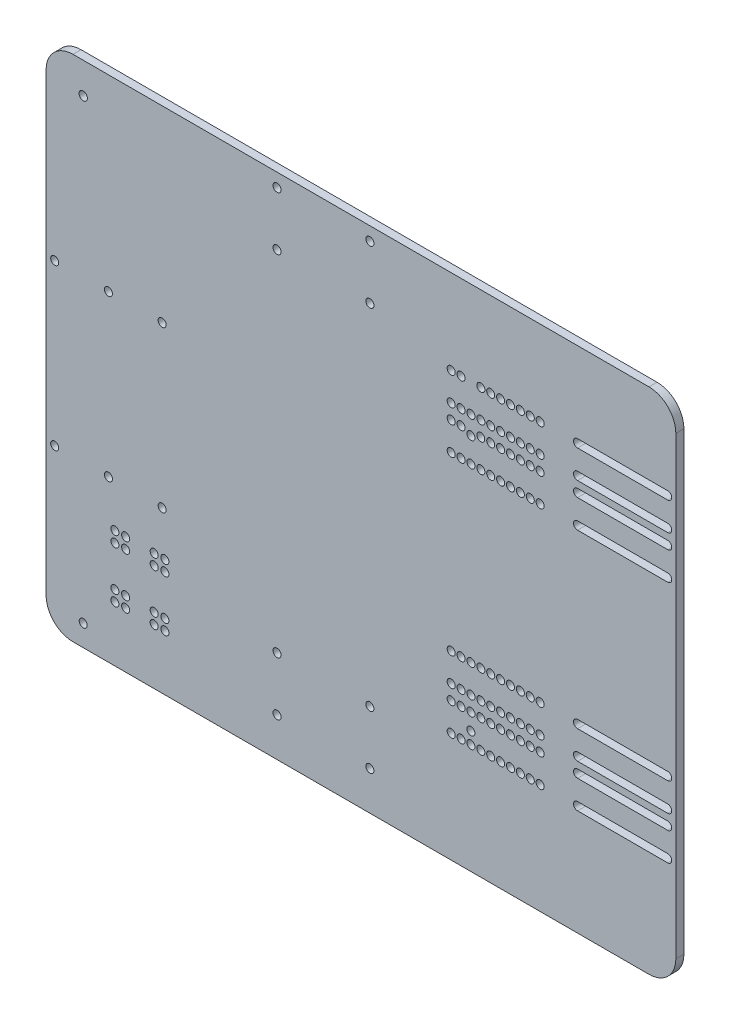
SolidWorks part; units mm, degrees
ref_plane "前视基准面" through (0, 0, 0) normal (0, 0, 1) x (1, 0, 0)
ref_plane "上视基准面" through (0, 0, 0) normal (0, 1, 0) x (1, 0, 0)
ref_plane "右视基准面" through (0, 0, 0) normal (1, 0, 0) x (0, 0, -1)
sketch "草图1" plane through (0, 0, 0) normal (0, 0, 1) x (1, 0, 0)
  line L1 (-115.5855, 94.5486) -> (118.873, 94.5486)
  line L2 (-115.5855, 94.5486) -> (-115.5855, -94.8828)
  line L3 (-115.5855, -94.8828) -> (118.873, -94.8828)
  line L4 (118.873, 94.5486) -> (118.873, -94.8828)
  circle A3 centre (-72.3857, 24.6381) radius 1.5
  circle A16 centre (-72.3857, -35.082) radius 1.5
extrude "凸台-拉伸1" add sketch "草图1" along normal blind 3
fillet "圆角1" radius 10 4 edges at (118.873, 94.5486, 1.5) (-115.5855, 94.5486, 1.5) (-115.5855, -94.8828, 1.5) (118.873, -94.8828, 1.5)
sketch "草图2" plane through (0, 0, 3) normal (0, 0, 1) x (1, 0, 0)
  line L1 (-105.5855, -94.8828) -> (108.873, -94.8828) construction
  circle A0 centre (-71.363, -51.2228) radius 1.5
  circle A1 centre (-71.363, -70.2228) radius 1.5
  circle A2 centre (-85.983, -51.2228) radius 1.5
  circle A3 centre (-85.983, -70.2228) radius 1.5
  circle A8 centre (-85.983, -51.2228) radius 1.5
  circle A9 centre (-71.363, -51.2228) radius 1.5
  circle A10 centre (-85.983, -70.2228) radius 1.5
  circle A11 centre (-71.363, -70.2228) radius 1.5
  circle A12 centre (-89.983, -51.2228) radius 1.5
  circle A13 centre (-75.363, -51.2228) radius 1.5
  circle A14 centre (-89.983, -70.2228) radius 1.5
  circle A15 centre (-75.363, -70.2228) radius 1.5
  circle A28 centre (-85.983, -51.2228) radius 1.5
  circle A29 centre (-71.363, -51.2228) radius 1.5
  circle A30 centre (-85.983, -70.2228) radius 1.5
  circle A31 centre (-71.363, -70.2228) radius 1.5
  circle A32 centre (-89.983, -51.2228) radius 1.5
  circle A34 centre (-75.363, -51.2228) radius 1.5
  circle A36 centre (-89.983, -70.2228) radius 1.5
  circle A38 centre (-75.363, -70.2228) radius 1.5
  circle A40 centre (-85.983, -55.2228) radius 1.5
  circle A41 centre (-71.363, -55.2228) radius 1.5
  circle A42 centre (-85.983, -74.2228) radius 1.5
  circle A43 centre (-71.363, -74.2228) radius 1.5
  circle A44 centre (-89.983, -55.2228) radius 1.5
  circle A46 centre (-75.363, -55.2228) radius 1.5
  circle A48 centre (-89.983, -74.2228) radius 1.5
  circle A50 centre (-75.363, -74.2228) radius 1.5
  circle A52 centre (-89.983, -47.2228) radius 1.5 [skipped]
  circle A53 centre (-85.983, -47.2228) radius 1.5 [skipped]
  circle A55 centre (-75.363, -47.2228) radius 1.5 [skipped]
  circle A56 centre (-71.363, -47.2228) radius 1.5 [skipped]
  circle A58 centre (-89.983, -66.2228) radius 1.5 [skipped]
  circle A59 centre (-85.983, -66.2228) radius 1.5 [skipped]
  circle A61 centre (-75.363, -66.2228) radius 1.5 [skipped]
  circle A62 centre (-71.363, -66.2228) radius 1.5 [skipped]
  circle A64 centre (-81.983, -51.2228) radius 1.5 [skipped]
  circle A65 centre (-81.983, -70.2228) radius 1.5 [skipped]
  circle A66 centre (-67.363, -51.2228) radius 1.5 [skipped]
  circle A67 centre (-67.363, -70.2228) radius 1.5 [skipped]
  dimension "D1" = 3
  dimension "D5" = 3
  dimension "D6" = 3
  dimension "D7" = 14.62
  dimension "D8" = 3
  dimension "D3" = 43.66
  dimension "D4" = 19
  dimension "D9" = 2
  dimension "D10" = 2
  dimension "D11" = 2
  dimension "D12" = 2
extrude "切除-拉伸1" cut sketch "草图2" against normal through all contours A48 | A0 | A13 | A2 | A12 | A44 | A40 | A46 | A41 | A1 | A15 | A3 | A14 | A42 | A50 | A43 region at (-89.983, -74.2228, 3)
sketch "草图4" plane through (0, 0, 3) normal (0, 0, 1) x (1, 0, 0)
  circle A4 centre (-101.767, 83.0486) radius 1.5704
  circle A5 centre (-101.767, -86.9514) radius 1.5
  circle A6 centre (42.5819, 45.6694) radius 1.5
  circle A7 centre (42.5819, -49.5721) radius 1.5
  circle A13 centre (-112.3857, 24.6381) radius 1.5
  circle A16 centre (-112.3857, -35.082) radius 1.5
  circle A17 centre (-92.3857, 24.6381) radius 1.5
  circle A18 centre (-92.3857, -35.082) radius 1.5
extrude "切除-拉伸2" cut sketch "草图4" against normal through all
sketch "草图6" plane through (0, 0, 3) normal (0, 0, 1) x (1, 0, 0)
  line L0 (-37.3236, 94.5486) -> (-16.1289, 94.5486)
  line L1 (-37.3236, -85.4514) -> (-37.3236, 94.5486)
  line L2 (-37.3236, -85.4514) -> (12.6764, -85.4514)
  line L3 (12.6764, -85.4514) -> (12.6764, 94.5486)
  line L4 (12.6764, 4.5486) -> (122.1564, 4.5486)
  line L5 (-16.1289, 94.5486) -> (-12.3236, 94.5486)
  line L10 (108.873, 94.5486) -> (-105.5855, 94.5486) construction
  line L11 (-12.3236, 94.5486) -> (12.6764, 94.5486)
  line L12 (47.6764, 111.2587) -> (47.6764, -114.1672)
  line L17 (91.3583, 51.0486) -> (115.854, 51.0486)
  line L19 (155.8937, -35.4514) -> (19.7198, -35.4514)
  line L24 (91.3583, 38.0486) -> (115.854, 38.0486)
  line L25 (91.3583, 35.0486) -> (115.854, 35.0486)
  line L30 (91.3583, 54.0486) -> (115.854, 54.0486)
  line L43 (91.3583, 45.5486) -> (115.854, 45.5486)
  line L44 (91.3583, 61.5486) -> (115.854, 61.5486)
  line L50 (155.8937, 55.0486) -> (23.4823, 55.0486)
  line L53 (91.3583, 64.5486) -> (115.854, 64.5486)
  line L54 (91.3583, 48.5486) -> (115.854, 48.5486)
  line L59 (32.6764, 113.2645) -> (32.6764, -109.5534)
  line L60 (91.3583, 64.5486) -> (82.2736, 64.5486)
  line L62 (82.2736, 61.5486) -> (91.3583, 61.5486)
  line L63 (91.3583, 54.0486) -> (82.2736, 54.0486)
  line L65 (82.2736, 51.0486) -> (91.3583, 51.0486)
  line L66 (91.3583, 48.5486) -> (82.2736, 48.5486)
  line L68 (82.2736, 45.5486) -> (91.3583, 45.5486)
  line L69 (91.3583, 38.0486) -> (82.2736, 38.0486)
  line L71 (82.2736, 35.0486) -> (91.3583, 35.0486)
  line L72 (82.2736, -25.9514) -> (91.3583, -25.9514)
  line L73 (91.3583, -28.9514) -> (82.2736, -28.9514)
  line L74 (82.2736, -36.4514) -> (91.3583, -36.4514)
  line L75 (91.3583, -39.4514) -> (82.2736, -39.4514)
  line L76 (82.2736, -41.9514) -> (91.3583, -41.9514)
  line L77 (91.3583, -44.9514) -> (82.2736, -44.9514)
  line L78 (82.2736, -52.4514) -> (91.3583, -52.4514)
  line L79 (91.3583, -55.4514) -> (82.2736, -55.4514)
  line L80 (91.3583, -39.4514) -> (115.854, -39.4514)
  line L81 (91.3583, -55.4514) -> (115.854, -55.4514)
  line L82 (91.3583, -52.4514) -> (115.854, -52.4514)
  line L83 (91.3583, -36.4514) -> (115.854, -36.4514)
  line L84 (91.3583, -44.9514) -> (115.854, -44.9514)
  line L85 (91.3583, -25.9514) -> (115.854, -25.9514)
  line L86 (91.3583, -28.9514) -> (115.854, -28.9514)
  line L87 (91.3583, -41.9514) -> (115.854, -41.9514)
  circle A14 centre (-29.6096, 89.5486) radius 1.5
  circle A15 centre (4.9625, -60.4514) radius 1.5
  circle A16 centre (-29.6096, -80.4514) radius 1.5
  circle A17 centre (4.9625, -80.4514) radius 1.5
  circle A18 centre (4.9625, 89.5486) radius 1.5
  circle A19 centre (-29.6096, 69.5486) radius 1.5
  circle A20 centre (-29.6096, -60.4514) radius 1.5
  circle A21 centre (-29.6096, -80.4514) radius 1.5
  circle A23 centre (49.9549, -27.4514) radius 1.5
  circle A24 centre (49.9549, -43.4514) radius 1.5
  circle A39 centre (53.6349, -27.4514) radius 1.5
  circle A40 centre (53.6349, -43.4514) radius 1.5
  circle A41 centre (57.3149, -27.4514) radius 1.5
  circle A42 centre (57.3149, -43.4514) radius 1.5
  circle A43 centre (60.9949, -27.4514) radius 1.5
  circle A44 centre (60.9949, -43.4514) radius 1.5
  circle A45 centre (64.6749, -27.4514) radius 1.5
  circle A46 centre (64.6749, -43.4514) radius 1.5
  circle A47 centre (68.3549, -27.4514) radius 1.5
  circle A48 centre (68.3549, -43.4514) radius 1.5
  circle A49 centre (68.3549, 52.5486) radius 1.5
  circle A50 centre (68.3549, 36.5486) radius 1.5
  circle A51 centre (64.6749, 52.5486) radius 1.5
  circle A52 centre (64.6749, 36.5486) radius 1.5
  circle A53 centre (60.9949, 52.5486) radius 1.5
  circle A54 centre (60.9949, 36.5486) radius 1.5
  circle A55 centre (57.3149, 52.5486) radius 1.5
  circle A56 centre (57.3149, 36.5486) radius 1.5
  circle A57 centre (53.6349, 52.5486) radius 1.5
  circle A58 centre (53.6349, 36.5486) radius 1.5
  arc A61 (115.854, 54.0486) -> (115.854, 51.0486) centre (115.854, 52.5486) cw
  arc A62 (115.854, 38.0486) -> (115.854, 35.0486) centre (115.854, 36.5486) cw
  circle A63 centre (49.9549, 52.5486) radius 1.5
  circle A64 centre (49.9549, 36.5486) radius 1.5
  circle A79 centre (68.3549, 63.0486) radius 1.5
  circle A80 centre (49.9549, 63.0486) radius 1.5
  circle A83 centre (57.3149, 63.0486) radius 1.5
  circle A86 centre (64.6749, 47.0486) radius 1.5
  circle A87 centre (49.9549, 47.0486) radius 1.5
  arc A89 (115.854, 48.5486) -> (115.854, 45.5486) centre (115.854, 47.0486) cw
  circle A90 centre (53.6349, 63.0486) radius 1.5
  circle A93 centre (60.9949, 63.0486) radius 1.5
  circle A95 centre (64.6749, 63.0486) radius 1.5
  circle A96 centre (57.3149, 47.0486) radius 1.5
  circle A97 centre (53.6349, 47.0486) radius 1.5
  arc A98 (115.854, 64.5486) -> (115.854, 61.5486) centre (115.854, 63.0486) cw
  circle A99 centre (60.9949, 47.0486) radius 1.5
  circle A100 centre (68.3549, 47.0486) radius 1.5
  circle A101 centre (49.9549, -37.9514) radius 1.5
  circle A102 centre (68.3549, -37.9514) radius 1.5
  circle A103 centre (60.9949, -37.9514) radius 1.5
  circle A104 centre (53.6349, -37.9514) radius 1.5
  circle A105 centre (57.3149, -37.9514) radius 1.5
  circle A109 centre (64.6749, -37.9514) radius 1.5
  circle A112 centre (49.9549, -53.9514) radius 1.5
  circle A114 centre (64.6749, -53.9514) radius 1.5
  circle A115 centre (60.9949, -53.9514) radius 1.5
  circle A117 centre (53.6349, -53.9514) radius 1.5
  circle A121 centre (57.3149, -53.9514) radius 1.5
  circle A122 centre (68.3549, -53.9514) radius 1.5
  circle A123 centre (4.9625, 69.5486) radius 1.5
  circle A124 centre (46.2749, 63.0486) radius 1.5
  circle A125 centre (46.2749, 52.5486) radius 1.5
  circle A126 centre (46.2749, 47.0486) radius 1.5
  circle A127 centre (46.2749, 36.5486) radius 1.5
  circle A128 centre (46.2749, -27.4514) radius 1.5
  circle A129 centre (46.2749, -37.9514) radius 1.5
  circle A130 centre (46.2749, -43.4514) radius 1.5
  circle A131 centre (46.2749, -53.9514) radius 1.5
  circle A133 centre (42.5949, 52.5486) radius 1.5
  circle A135 centre (42.5949, 36.5486) radius 1.5
  circle A136 centre (42.5949, -27.4514) radius 1.5
  circle A137 centre (42.5949, -37.9514) radius 1.5
  circle A138 centre (42.5949, -43.4514) radius 1.5
  circle A139 centre (42.5949, -53.9514) radius 1.5
  circle A140 centre (38.9149, 63.0486) radius 1.5
  circle A141 centre (38.9149, 52.5486) radius 1.5
  circle A142 centre (38.9149, 47.0486) radius 1.5
  circle A143 centre (38.9149, 36.5486) radius 1.5
  circle A144 centre (38.9149, -27.4514) radius 1.5
  circle A145 centre (38.9149, -37.9514) radius 1.5
  circle A146 centre (38.9149, -43.4514) radius 1.5
  circle A147 centre (38.9149, -53.9514) radius 1.5
  circle A148 centre (35.2349, 63.0486) radius 1.5
  circle A149 centre (35.2349, 52.5486) radius 1.5
  circle A150 centre (35.2349, 47.0486) radius 1.5
  circle A151 centre (35.2349, 36.5486) radius 1.5
  circle A152 centre (35.2349, -27.4514) radius 1.5
  circle A153 centre (35.2349, -37.9514) radius 1.5
  circle A154 centre (35.2349, -43.4514) radius 1.5
  circle A155 centre (35.2349, -53.9514) radius 1.5
  circle A156 centre (42.5949, 47.0486) radius 1.5 [skipped]
  circle A157 centre (42.5949, 63.0486) radius 1.5 [skipped]
  arc A158 (82.2736, 61.5486) -> (82.2736, 64.5486) centre (82.2736, 63.0486) cw
  arc A159 (82.2736, 51.0486) -> (82.2736, 54.0486) centre (82.2736, 52.5486) cw
  arc A160 (82.2736, 45.5486) -> (82.2736, 48.5486) centre (82.2736, 47.0486) cw
  arc A161 (82.2736, 35.0486) -> (82.2736, 38.0486) centre (82.2736, 36.5486) cw
  arc A162 (82.2736, -25.9514) -> (82.2736, -28.9514) centre (82.2736, -27.4514) ccw
  arc A163 (82.2736, -36.4514) -> (82.2736, -39.4514) centre (82.2736, -37.9514) ccw
  arc A164 (82.2736, -41.9514) -> (82.2736, -44.9514) centre (82.2736, -43.4514) ccw
  arc A165 (82.2736, -52.4514) -> (82.2736, -55.4514) centre (82.2736, -53.9514) ccw
  arc A166 (115.854, -55.4514) -> (115.854, -52.4514) centre (115.854, -53.9514) ccw
  arc A167 (115.854, -39.4514) -> (115.854, -36.4514) centre (115.854, -37.9514) ccw
  arc A168 (115.854, -28.9514) -> (115.854, -25.9514) centre (115.854, -27.4514) ccw
  arc A169 (115.854, -44.9514) -> (115.854, -41.9514) centre (115.854, -43.4514) ccw
  point P0 (-12.3236, 94.5486)
  point P53 (-12.3236, 94.5486)
  dimension "D1" = 35
  dimension "D2" = 40
  dimension "D3" = 6
  dimension "D4" = 50.5
  dimension "D6" = 20
  dimension "D7" = 5
extrude "切除-拉伸3" cut sketch "草图6" against normal through all contours A159 L65 L17 A61 L30 L63 | A126 L12 | A142 | A141 | A140 | A148 | A149 | A14 | A19 | A18 | A123 | A80 | A90 | A83 | A93 | L53 A98 L44 L62 A158 L60 | L54 A89 L43 L68 A160 L66 | L24 A62 L25 L71 A161 L69 | A79 | A95 | A63 | A87 | A57 | A55 | A53 | A51 | A49 | A100 | A50 | A86 | A99 | A96 | A97 | A64 | A58 | A56 | A54 | A52 | A47 | A45 | A43 | A41 | A39 | A23 | A101 | A104 | A105 | A103 | A109 | A102 | A48 | A122 | A46 | A114 | A44 | A115 | A42 | A121 | A40 | A117 | A24 | A112 | A20 | A16 | A15 | A17 | A133 | A125 | A124 | A150 | A151 | A143 | A135 | A127 | L65 L17 A61 L30 L63 A159 | A142 | L86 A168 L85 L72 A162 L73 | L80 A167 L83 L74 A163 L75 | L84 A169 L87 L76 A164 L77 | L81 A166 L82 L78 A165 L79 | A152 | A144 | A136 | A128 | A129 | A137 | A145 | A153 | A154 | A146 | A138 | A130 | A131 | A139 | A147 | A155 region at (46.2603, 47.0486, 3) region at (99.0638, 52.5486, 3) region at (38.9149, 63.0486, 3) region at (38.9149, 52.5486, 3) region at (38.9149, 47.0486, 3) region at (35.2349, 63.0486, 3) region at (35.2349, 52.5486, 3)
